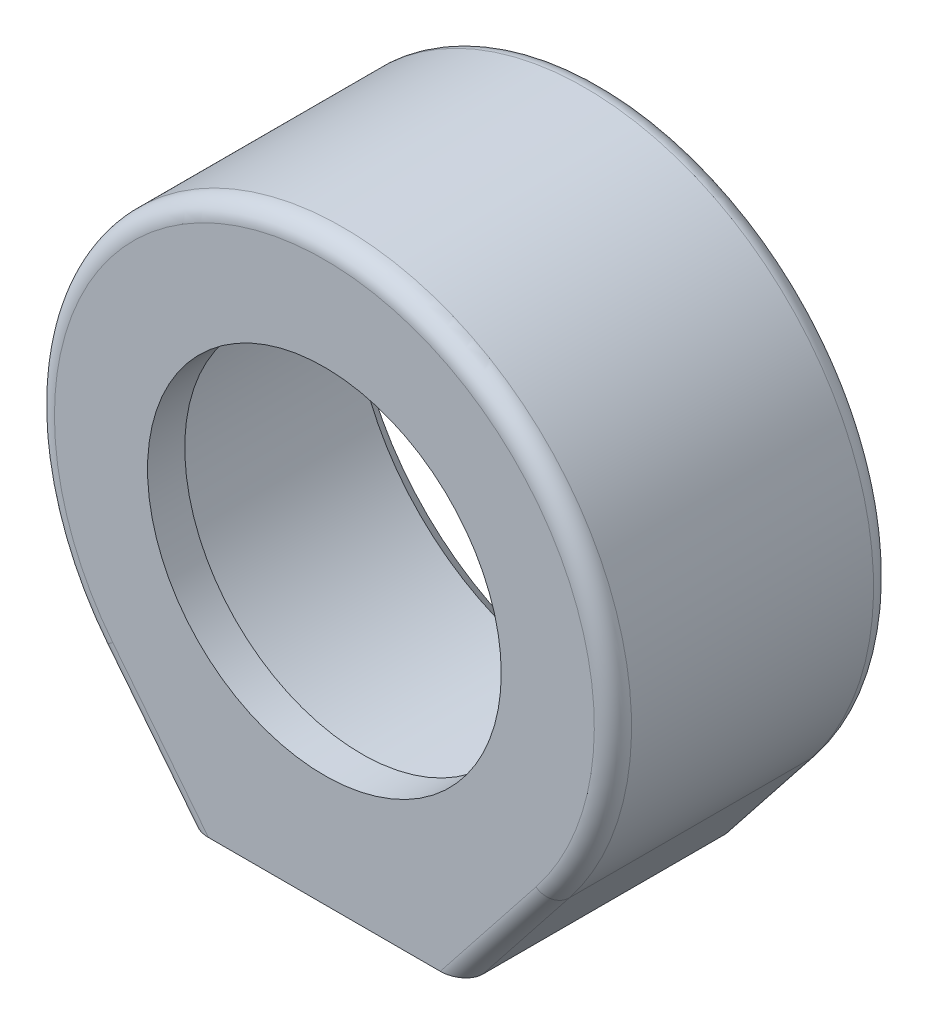
SolidWorks part; units mm, degrees
ref_plane "Ebene vorne" through (0, 0, 0) normal (0, 0, 1) x (1, 0, 0)
ref_plane "Ebene oben" through (0, 0, 0) normal (0, 1, 0) x (1, 0, 0)
ref_plane "Ebene rechts" through (0, 0, 0) normal (1, 0, 0) x (0, 0, -1)
sketch "Skizze1" plane through (0, 0, 0) normal (0, 0, 1) x (1, 0, 0)
  circle A0 centre (0, 0) radius 12.5
  circle A1 centre (0, 0) radius 15.5
  dimension "D1" = 25
  dimension "D2" = 3
extrude "Aufsatz-Linear austragen1" add sketch "Skizze1" along normal blind 15
sketch "Skizze2" plane through (0, 0, 15) normal (0, 0, 1) x (1, 0, 0)
  circle A0 centre (0, 0) radius 12.5 construction
  circle A1 centre (0, 0) radius 12.5
  circle A2 centre (0, 0) radius 9.5
  dimension "D1" = 3
extrude "Aufsatz-Linear austragen2" add sketch "Skizze2" against normal blind 2
sketch "Skizze3" plane through (0, 0, 15) normal (0, 0, 1) x (1, 0, 0)
  line L0 (0, 0) -> (0, -15.5) construction
  line L1 (7.5, -15.5) -> (-7.5, -15.5)
  line L2 (-7.5, -15.5) -> (-12.1543, -9.6189)
  line L3 (7.5, -15.5) -> (12.1543, -9.6189)
  circle A0 centre (0, 0) radius 15.5 construction
  arc A1 (-12.1543, -9.6189) -> (12.1543, -9.6189) centre (0, 0) ccw
  circle M4 centre (0, 0) radius 15.5
  dimension "D1" = 15
extrude "Aufsatz-Linear austragen3" add sketch "Skizze3" against normal through all contours L2 L1 M4 | L1 L3 M4 region at (6.9104, -14.2815, 15) region at (-6.9104, -14.2815, 15)
fillet "Verrundung1" radius 1 6 edges at (9.8272, -12.5594, 0) (-9.8272, -12.5594, 0) (9.8272, -12.5594, 15) (-9.8272, -12.5594, 15) (0, 15.5, 0) (0, 15.5, 15)
chamfer "Fase1" distance 1 angle 45 1 edges at (12.5, 0, 0)
